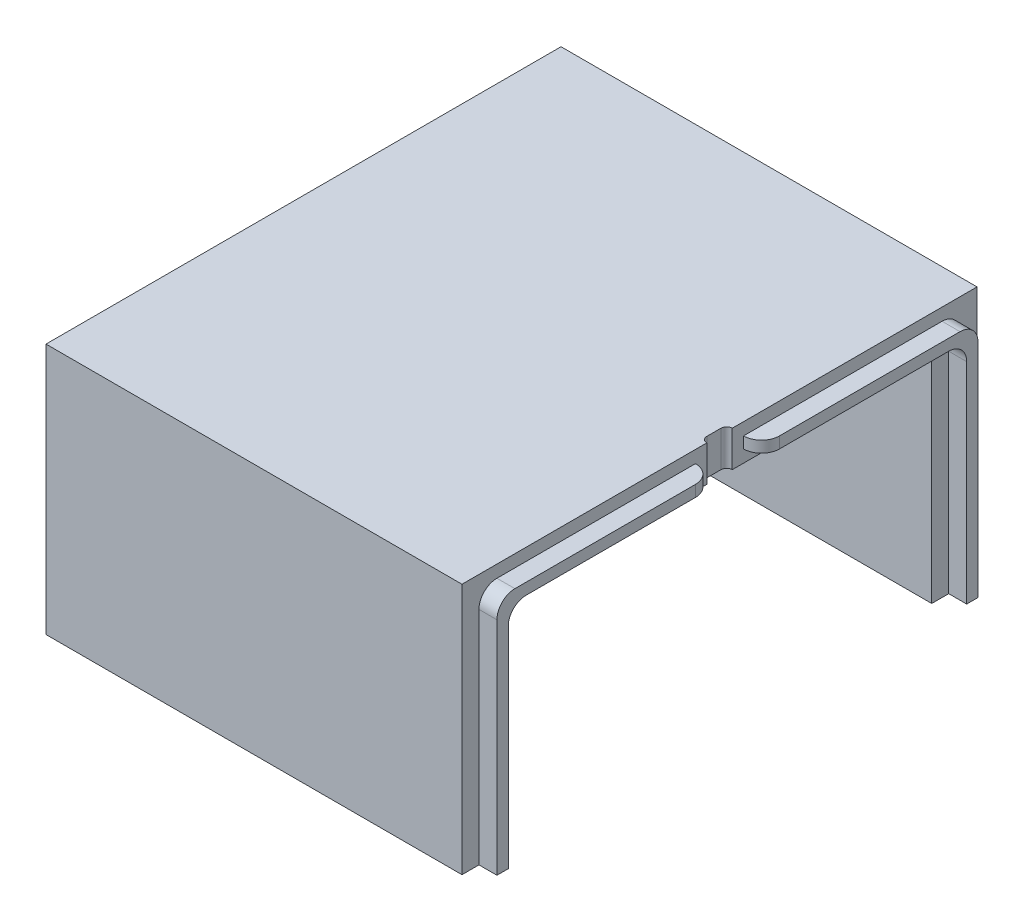
SolidWorks part; units mm, degrees
material "6061 Alloy"
ref_plane "Front Plane" through (0, 0, 0) normal (0, 0, 1) x (1, 0, 0)
ref_plane "Top Plane" through (0, 0, 0) normal (0, 1, 0) x (1, 0, 0)
ref_plane "Right Plane" through (0, 0, 0) normal (1, 0, 0) x (0, 0, -1)
sketch "MainSketch" plane through (0, 0, 0) normal (0, 1, 0) x (1, 0, 0)
  line L0 (0, -4) -> (-32.75, -4)
  line L1 (0, 0) -> (-36.75, 0)
  line L2 (0, 0) -> (0, -45.5)
  line L3 (0, -45.5) -> (-36.75, -45.5)
  line L4 (-36.75, 0) -> (-36.75, -45.5)
  line L5 (-32.75, -4) -> (-32.75, -41.5)
  line L6 (-32.75, -41.5) -> (0, -41.5)
  line L7 (31.75, -5) -> (-31.75, -5) construction
  line L8 (-31.75, -5) -> (-31.75, -40.5) construction
  line L9 (-31.75, -40.5) -> (31.75, -40.5) construction
  line L10 (0, -22.125) -> (0, -23.375) construction
  line L11 (0.5, -22.125) -> (0.5, -23.375)
  line L12 (-0.5, -22.125) -> (-0.5, -23.375)
  arc A0 (0.5, -22.125) -> (-0.5, -22.125) centre (0, -22.125) ccw
  arc A1 (-0.5, -23.375) -> (0.5, -23.375) centre (0, -23.375) ccw
  point P7 (-10, -2.5)
  point P10 (-34.25, -2.5)
  point P11 (-34.25, -43)
  point P12 (-10, -43)
  point P17 (0, -22.75)
  point P24 (-18.375, -2.5)
  point P25 (0, 0)
  point P26 (-18.375, -43)
  point P27 (0, 0)
  dimension "D14" = 0.5
  dimension "D1" = 4
  dimension "D2" = 4
  dimension "D3" = 4
  dimension "D4" = 36.75
  dimension "D6" = 5
  dimension "D7" = 5
  dimension "D8" = 5
  dimension "D9" = 2.5
  dimension "D10" = 2.5
  dimension "D11" = 10
  dimension "D12" = 10
  dimension "D13" = 2.5
  dimension "D15" = 1.25
  dimension "D5" = 35.5
  dimension "D16" = 63.5
  dimension "D17" = 18.375
extrude "Wall" add sketch "MainSketch" along normal blind 19.05 contours L6 L5 L0 L2 L1 L4 L3 region at (-16.375, 0, 3.4151)
extrude "Roof" add sketch "MainSketch<3>" along normal blind 3.175 from surface contours L5 L6 L2 L0 | L6 L5 L0 L2 L1 L4 L3 region at (-16.3884, 0, 22.75) region at (-16.375, 0, 3.4151) starting at face at (-17.375, 19.05, 22.75)
sketch "MainSketch<3>" plane through (0, 0, 0) normal (0, 1, 0) x (1, 0, 0) same geometry as "MainSketch"
hole_wizard "#2-56 Tapped Hole1" positions "3DSketch1" profile "Sketch2" tap size "#2-56" standard "ANSI Inch"
sketch3d "3DSketch1"
  point P19 (-18.375, 0, 43)
  point P22 (-18.375, 0, 2.5)
  point P27 (0, 0, 0)
  point P28 (0, 0, 0)
sketch "Sketch2" plane through (-18.375, 0, 43) normal (1, 0, 0) x (0, 0, -1)
  line L0 (0, 0) -> (0, 6.2642)
  line L1 (0, 6.2642) -> (0.889, 5.73)
  line L2 (0.889, 5.73) -> (0.889, 0)
  line L5 (0.889, 0) -> (0, 0)
  line L10 (0, 6.2642) -> (-0.889, 5.73) construction
  line L11 (0, -6.35) -> (0, 107.95) construction
  dimension "Tap Drill Dia." = 1.778
  dimension "Tap Drill Depth" = 5.73
  dimension "Drill Angle" = 118
cosmetic thread "Hole Thread1" parameters "D1"=4.37, "D2"=2.1844
cosmetic thread "Hole Thread2" parameters "D1"=4.37, "D2"=2.1844
sketch "Sketch3" plane through (0, 0, 0) normal (1, 0, 0) x (0, 0, -1)
  line L0 (-44, 0) -> (-44, 21.1375)
  line L1 (-41.5, 0) -> (-45.5, 0) construction
  line L2 (-44, 21.1375) -> (-1.5, 21.1375)
  line L3 (-1.5, 21.1375) -> (-1.5, 0)
  line L4 (0, 0) -> (-4, 0) construction
  line L5 (-43, 0) -> (-43, 20.1375)
  line L6 (-43, 20.1375) -> (-2.5, 20.1375)
  line L7 (-2.5, 20.1375) -> (-2.5, 0)
  line L8 (-44, 0) -> (-43, 0) construction
  line L9 (-45.5, 22.225) -> (-45.5, 0) construction
  line L10 (-2.5, 0) -> (-1.5, 0)
  line L11 (0, 22.225) -> (0, 0) construction
  line L12 (-22.75, 21.1375) -> (-22.75, 20.1375) construction
  line L13 (-21.625, 22.225) -> (0, 22.225) construction
  line L14 (-23.875, 22.225) -> (-23.875, 19.05) construction
  line L15 (-44, 0) -> (-43, 0)
  line L16 (-24.875, 21.1375) -> (-24.875, 20.1375)
  line L17 (-20.625, 21.1375) -> (-20.625, 20.1375)
  line L20 (-21.625, 22.225) -> (-21.625, 19.05) construction
  point P10 (-43.5, 0)
  point P15 (-2, 0)
  point P20 (-22.75, 20.6375)
  dimension "D1" = 1
  dimension "D2" = 1
  dimension "D3" = 1
  dimension "D4" = 2
  dimension "D5" = 2
  dimension "D6" = 1.5875
  dimension "D7" = 1
  dimension "D8" = 1
extrude "Boss-Extrude1" add sketch "Sketch3" along normal blind 1.5875 contours L16 L2 L0 L15 L5 L6 | L2 L17 L6 L7 L10 L3 region at (0, 10.5687, 43.7149) region at (0, 20.8524, 11.0625)
fillet "Fillet1" radius 1.5875 6 edges at (0.7937, 20.1375, 43) (0.7937, 21.1375, 44) (0.7937, 20.1375, 2.5) (0.7937, 21.1375, 1.5) (1.5875, 20.6375, 20.625) (1.5875, 20.6375, 24.875)
equation "\"D2@MainSketch\" = \"D1@MainSketch\""
equation "\"D3@MainSketch\" = \"D2@MainSketch\""
equation "\"D7@MainSketch\" = \"D6@MainSketch\""
equation "\"D8@MainSketch\" = \"D6@MainSketch\""
equation "\"D9@MainSketch\" = \"D7@MainSketch\" / 2"
equation "\"D10@MainSketch\" = \"D9@MainSketch\""
equation "\"D12@MainSketch\" = \"D11@MainSketch\""
equation "\"D13@MainSketch\" = \"D10@MainSketch\""
equation "\"D4@MainSketch\"=(\"D16@MainSketch\"+\"D6@MainSketch\"*2)/2"
equation "\"D3@Sketch3\"=\"D2@Sketch3\""
equation "\"D1@Sketch3\"=\"D3@Sketch3\""
equation "\"D5@Sketch3\"=\"D4@Sketch3\""
equation "\"side_thick\"= 4"
equation "\"D1@MainSketch\"=\"side_thick\""
equation "\"top_thick\"=3.175"
equation "\"D1@Roof\"=\"top_thick\""
equation "\"D6@Sketch3\"=\"top_thick\"/2"
equation "\"D4@Sketch3\"=\"side_thick\"/2"
equation "\"D17@MainSketch\"=\"D4@MainSketch\"/2"
